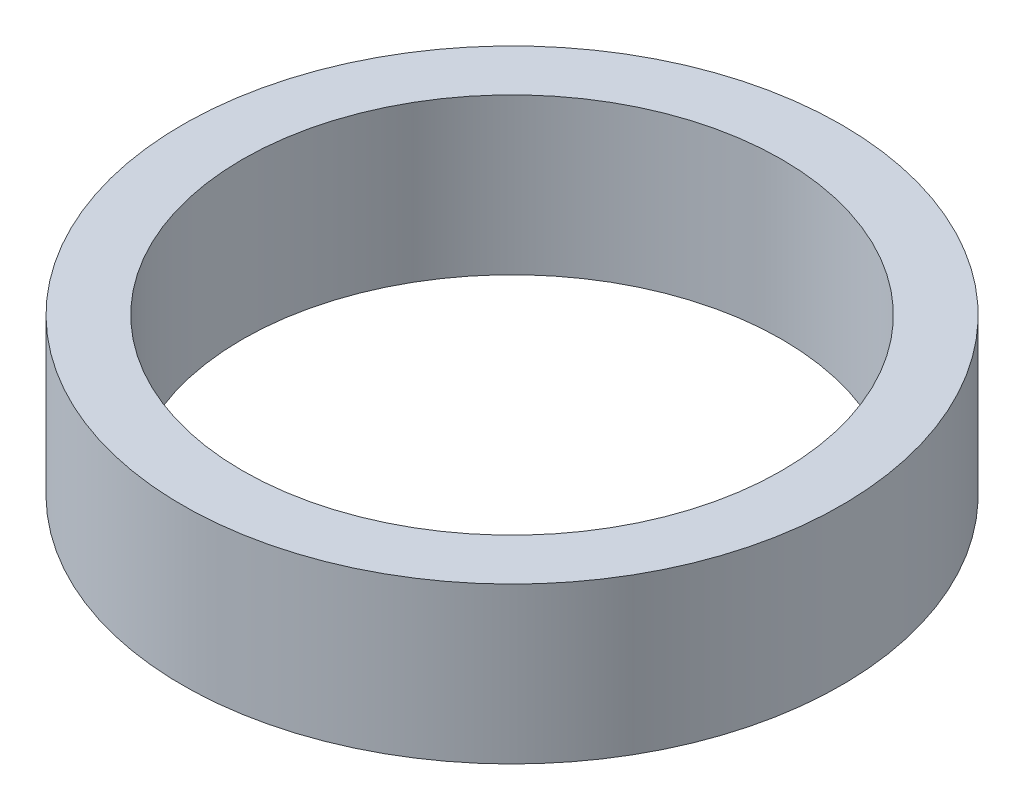
SolidWorks part; units mm, degrees
ref_plane "Front Plane" through (0, 0, 0) normal (0, 0, 1) x (1, 0, 0)
ref_plane "Top Plane" through (0, 0, 0) normal (0, 1, 0) x (1, 0, 0)
ref_plane "Right Plane" through (0, 0, 0) normal (1, 0, 0) x (0, 0, -1)
sketch "Sketch1" plane through (0, 0, 0) normal (0, 1, 0) x (1, 0, 0)
  circle A0 centre (0, 0) radius 55
  dimension "FLANGE_OD" = 110
extrude "Boss-Extrude1" add sketch "Sketch1" along normal blind 26
sketch "Sketch2" plane through (0, 0, 0) normal (0, 1, 0) x (1, 0, 0)
  circle A0 centre (0, 0) radius 45
  dimension "BORE_D" = 90
extrude "Cut-Extrude1" cut sketch "Sketch2" along normal through all
sketch "Sketch3" plane through (0, 26, 0) normal (0, 1, 0) x (1, 0, 0)
  circle A0 centre (0, 0) radius 23.9303 construction
  circle A1 centre (-23.9303, 0) radius 1.7434
  dimension "BOLT_D" = 3.4869
  dimension "BOLT_PCD" = 47.8605
extrude "Cut-Extrude2" cut sketch "Sketch3" against normal blind 17.9027 rebuild error yes
pattern_circular "CirPattern1" count 5 over 360 rebuild error yes
